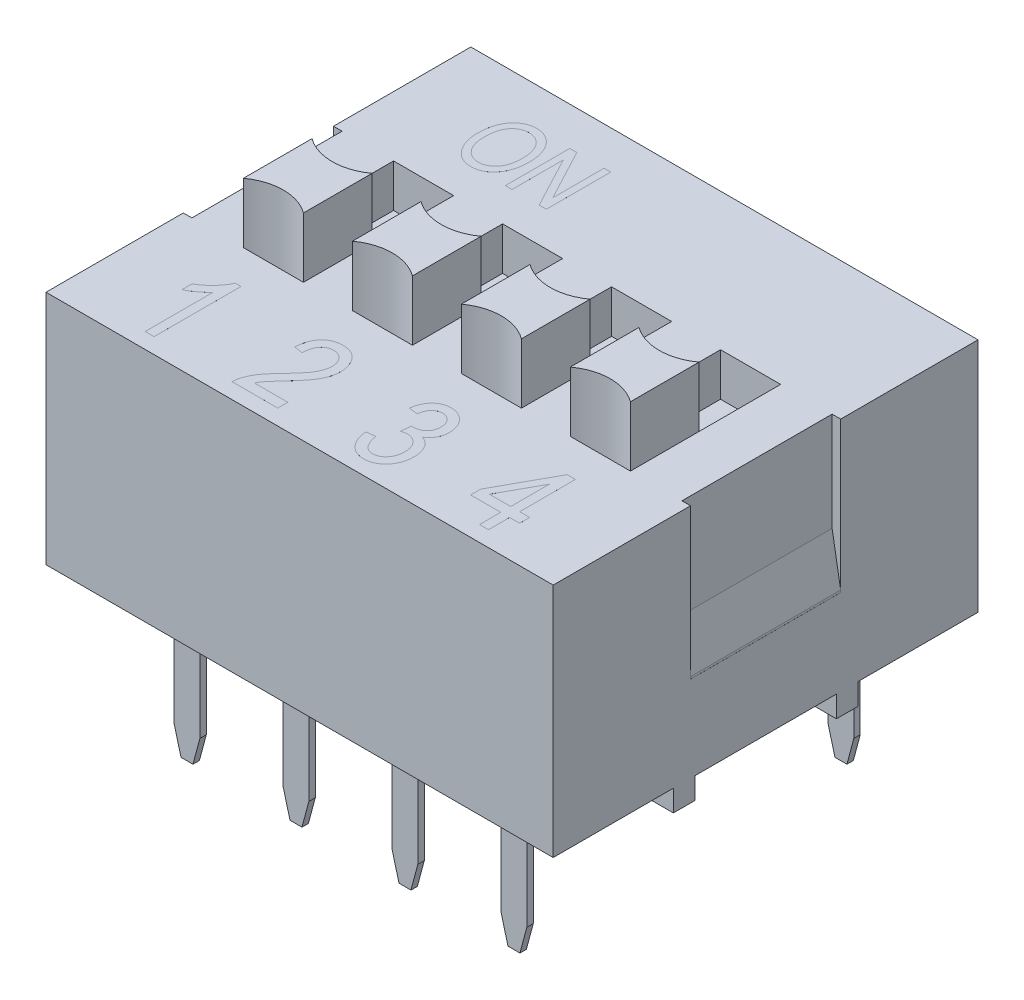
SolidWorks part; units mm, degrees
ref_plane "Front" through (0, 0, 0) normal (0, 0, 1) x (1, 0, 0)
ref_plane "Top" through (0, 0, 0) normal (0, 1, 0) x (1, 0, 0)
ref_plane "Right" through (0, 0, 0) normal (1, 0, 0) x (0, 0, -1)
sketch "Эскиз1" plane through (0, 0, 0) normal (0, 1, 0) x (1, 0, 0)
  line L1 (0, 0) -> (11.82, 0)
  line L2 (0, 0) -> (0, 9.9)
  line L3 (0, 9.9) -> (11.82, 9.9)
  line L4 (11.82, 0) -> (11.82, 9.9)
  dimension "D1" = 11.82
  dimension "D2" = 9.9
extrude "Бобышка-Вытянуть1" add sketch "Эскиз1" along normal blind 5.5
sketch "Эскиз2" plane through (0, 5.5, 0) normal (0, 1, 0) x (1, 0, 0)
  line L0 (0, 4.95) -> (11.82, 4.95) construction
  line L1 (0, 9.9) -> (0, 0) construction
  line L2 (11.82, 0) -> (11.82, 9.9) construction
  line L3 (3.94, 3.2) -> (3.94, 6.7)
  line L4 (1.4, 3.2) -> (2.8, 3.2)
  line L5 (1.4, 3.2) -> (1.4, 6.7)
  line L6 (1.4, 6.7) -> (2.8, 6.7)
  line L7 (2.8, 3.2) -> (2.8, 6.7)
  line L8 (1.4, 3.2) -> (2.8, 6.7) construction
  line L9 (1.4, 6.7) -> (2.8, 3.2) construction
  line L10 (3.94, 3.2) -> (5.34, 3.2)
  line L11 (5.34, 3.2) -> (5.34, 6.7)
  line L12 (3.94, 6.7) -> (5.34, 6.7)
  line L13 (6.48, 3.2) -> (6.48, 6.7)
  line L14 (6.48, 3.2) -> (7.88, 3.2)
  line L15 (7.88, 3.2) -> (7.88, 6.7)
  line L16 (6.48, 6.7) -> (7.88, 6.7)
  line L17 (9.02, 3.2) -> (9.02, 6.7)
  line L18 (9.02, 3.2) -> (10.42, 3.2)
  line L19 (10.42, 3.2) -> (10.42, 6.7)
  line L20 (9.02, 6.7) -> (10.42, 6.7)
  point P6 (2.1, 4.95)
  dimension "D1" = 1.4
  dimension "D2" = 3.5
  dimension "D3" = 2.1
  dimension "D4" = 4
extrude "Вырез-Вытянуть1" cut sketch "Эскиз2" against normal blind 1
sketch "Эскиз3" plane through (0, 4.5, 0) normal (0, 1, 0) x (1, 0, 0)
  line L0 (1.4, 4) -> (2.8, 4) construction
  line L2 (1.4, 4.8) -> (1.4, 3.2)
  line L4 (2.8, 4.8) -> (2.8, 3.2)
  line L5 (1.4, 4.8) -> (2.8, 3.2) construction
  line L6 (1.4, 3.2) -> (2.8, 4.8) construction
  line L7 (3.94, 4.8) -> (3.94, 3.2)
  line L8 (5.34, 4.8) -> (5.34, 3.2)
  line L9 (6.48, 4.8) -> (6.48, 3.2)
  line L10 (7.88, 4.8) -> (7.88, 3.2)
  line L11 (9.02, 4.8) -> (9.02, 3.2)
  line L12 (10.42, 4.8) -> (10.42, 3.2)
  arc A0 (1.4, 4.8) -> (2.8, 4.8) centre (2.1, 5.7531) ccw
  arc A1 (1.4, 3.2) -> (2.8, 3.2) centre (2.1, 2.2469) cw
  arc A2 (3.94, 4.8) -> (5.34, 4.8) centre (4.64, 5.7531) ccw
  arc A3 (3.94, 3.2) -> (5.34, 3.2) centre (4.64, 2.2469) cw
  arc A4 (6.48, 4.8) -> (7.88, 4.8) centre (7.18, 5.7531) ccw
  arc A5 (6.48, 3.2) -> (7.88, 3.2) centre (7.18, 2.2469) cw
  arc A6 (9.02, 4.8) -> (10.42, 4.8) centre (9.72, 5.7531) ccw
  arc A7 (9.02, 3.2) -> (10.42, 3.2) centre (9.72, 2.2469) cw
  point P0 (2.1, 4)
  dimension "D1" = 1.6
  dimension "D2" = 1.4
  dimension "D3" = 4
extrude "Бобышка-Вытянуть2" add sketch "Эскиз3" along normal blind 2.4
sketch "Эскиз4" plane through (11.82, 0, 0) normal (1, 0, 0) x (0, 0, -1)
  line L0 (0, 5.5) -> (9.9, 5.5) construction
  line L1 (3.2, 5.5) -> (6.7, 5.5)
  line L2 (3.2, 5.5) -> (3.2, 2)
  line L3 (3.2, 2) -> (6.7, 2)
  line L4 (6.7, 5.5) -> (6.7, 2)
  dimension "D1" = 0
  dimension "D2" = 3.5
  dimension "D3" = 3.5
extrude "Вырез-Вытянуть2" cut sketch "Эскиз4" against normal blind 0.2
sketch "Эскиз5" plane through (11.62, 0, 0) normal (1, 0, 0) x (0, 0, -1)
  line L0 (6.7, 2) -> (6.7, 5.5) construction
  line L1 (3.2, 2) -> (6.7, 2)
  line L2 (3.2, 2) -> (3.2, 3.2)
  line L3 (3.2, 3.2) -> (6.7, 3.2)
  line L4 (6.7, 2) -> (6.7, 3.2)
  dimension "D1" = 1.2
extrude "Бобышка-Вытянуть3" add sketch "Эскиз5" along normal blind 0.199
chamfer "Фаска1" distance 0.2 distance2 1.15 1 edges at (11.819, 3.2, -4.95) first distance on face at (11.7195, 3.2, -4.95)
sketch "Эскиз6" plane through (0, 0, 0) normal (-1, 0, 0) x (0, 0, 1)
  line L0 (-9.9, 5.5) -> (0, 5.5) construction
  line L1 (-6.7, 5.5) -> (-3.2, 5.5)
  line L2 (-6.7, 5.5) -> (-6.7, 2)
  line L3 (-6.7, 2) -> (-3.2, 2)
  line L4 (-3.2, 5.5) -> (-3.2, 2)
  dimension "D1" = 0
  dimension "D2" = 3.5
  dimension "D3" = 3.5
extrude "Вырез-Вытянуть3" cut sketch "Эскиз6" against normal blind 0.2
sketch "Эскиз7" plane through (0.2, 0, 0) normal (-1, 0, 0) x (0, 0, 1)
  line L0 (-3.2, 2) -> (-3.2, 5.5) construction
  line L1 (-6.7, 2) -> (-3.2, 2)
  line L2 (-6.7, 2) -> (-6.7, 3.2)
  line L3 (-6.7, 3.2) -> (-3.2, 3.2)
  line L4 (-3.2, 2) -> (-3.2, 3.2)
  dimension "D1" = 1.2
extrude "Бобышка-Вытянуть4" add sketch "Эскиз7" along normal blind 0.199
chamfer "Фаска2" distance 0.2 distance2 1.15 1 edges at (0.001, 3.2, -4.95) first distance on face at (0.1005, 3.2, -4.95)
sketch "Эскиз8" plane through (0, 5.5, 0) normal (0, 1, 0) x (1, 0, 0)
  line L0 (0.2679, 7.5052) -> (4.3112, 7.5052) construction
  line L1 (0, 0.3629) -> (11.82, 0.3629) construction
  line L2 (0, 3.2) -> (0, 0) construction
  line L3 (11.82, 0) -> (11.82, 3.2) construction
  text T0 "ON" font "Arial Narrow" height 1.5
  text T1 "  1  2  3  4" font "Arial Narrow" height 2
extrude "Бобышка-Вытянуть5" add sketch "Эскиз8" along normal blind 0.0001
sketch "Эскиз9" plane through (0, 0, 0) normal (0, -1, 0) x (1, 0, 0)
  line L0 (0, -9.9) -> (0, 0) construction
  line L1 (0, -2.8) -> (11.82, -2.8)
  line L2 (0, -2.8) -> (0, -3.3)
  line L3 (0, -3.3) -> (11.82, -3.3)
  line L4 (11.82, -2.8) -> (11.82, -3.3)
  line L5 (11.82, 0) -> (11.82, -9.9) construction
  line L6 (0, 0) -> (11.82, 0) construction
  line L7 (0, -6.6) -> (11.82, -6.6)
  line L8 (0, -6.6) -> (0, -7.1)
  line L9 (0, -7.1) -> (11.82, -7.1)
  line L10 (11.82, -6.6) -> (11.82, -7.1)
  line L11 (11.82, -9.9) -> (0, -9.9) construction
  dimension "D1" = 0.5
  dimension "D2" = 0.5
  dimension "D3" = 2.8
  dimension "D4" = 2.8
extrude "Бобышка-Вытянуть6" add sketch "Эскиз9" along normal blind 0.5
sketch "Эскиз10" plane through (0, 0, 0) normal (0, -1, 0) x (1, 0, 0)
  line L1 (0, -2.8) -> (0, 0) construction
  line L2 (1.8, -1.1857) -> (2.4, -1.1857)
  line L3 (1.8, -1.1857) -> (1.8, -1.3357)
  line L4 (1.8, -1.3357) -> (2.4, -1.3357)
  line L5 (2.4, -1.1857) -> (2.4, -1.3357)
  line L6 (1.8, -1.1857) -> (2.4, -1.3357) construction
  line L7 (1.8, -1.3357) -> (2.4, -1.1857) construction
  point P0 (2.1, -1.2607)
  dimension "D2" = 2.1
  dimension "D1" = 0.6
  dimension "D3" = 0.15
extrude "Бобышка-Вытянуть7" add sketch "Эскиз10" along normal blind 3.5
chamfer "Фаска3" distance 0.6 angle 15 2 edges at (1.8, -3.5, -1.2607) (2.4, -3.5, -1.2607) first distance on face at (1.8, -1.75, -1.2607) first distance on face at (2.4, -1.75, -1.2607)
pattern_linear "Линейный массив1" count 4 spacing 2.54 along (1, 0, 0) count 2 spacing 7.62 along (0, 0, -1) of "Бобышка-Вытянуть7", "Фаска3"
